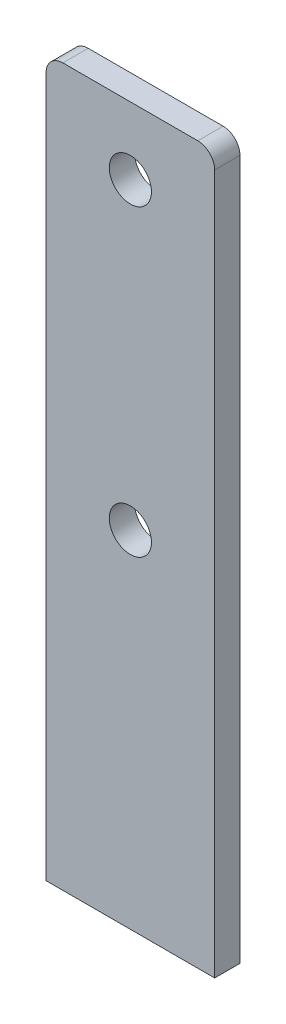
SolidWorks part; units mm, degrees
ref_plane "Alzado" through (0, 0, 0) normal (0, 0, 1) x (1, 0, 0)
ref_plane "Planta" through (0, 0, 0) normal (0, 1, 0) x (1, 0, 0)
ref_plane "Vista lateral" through (0, 0, 0) normal (1, 0, 0) x (0, 0, -1)
sketch "Croquis1" plane through (0, 0, 0) normal (0, 0, 1) x (1, 0, 0)
  line L5 (20, 0) -> (20, 83)
  line L6 (20, 0) -> (0, 0)
  line L7 (10, 0) -> (10, 85)
  line L8 (10, 20.31) -> (10, 79.5) construction
  line L9 (18, 85) -> (2, 85)
  line L10 (0, 0) -> (0, 83)
  line L11 (10, 0) -> (10, 10) construction
  circle A0 centre (10, 77) radius 2.5
  circle A1 centre (10, 41) radius 2.5
  arc A3 (2, 85) -> (0, 83) centre (2, 83) ccw
  arc A4 (18, 85) -> (20, 83) centre (18, 83) cw
  point P14 (0, 85)
  dimension "D2" = 5
  dimension "D8" = 2
  dimension "D1" = 10
  dimension "D4" = 31
  dimension "D6" = 85
  dimension "D7" = 10
  dimension "D3" = 2
extrude "Saliente-Extruir1" add sketch "Croquis1" along normal blind 3 contours L9 A3 L10 L7 A1 A0 | A4 L9 L7 A0 A1 L6 L5 region at (15.0885, 42.0659, 0) region at (4.9115, 42.0659, 0)
